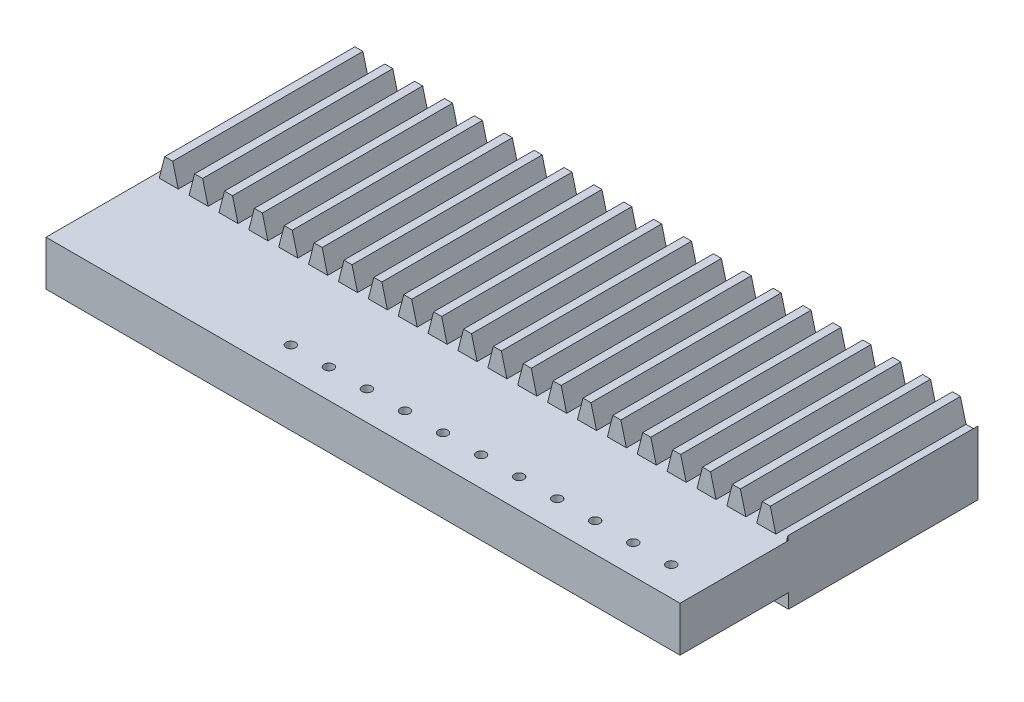
SolidWorks part; units mm, degrees
extrude "Blank" add sketch "BlankSke" against normal blind 20
sketch "BlankSke" plane through (0, 0, 0) normal (0, 0, 1) x (1, 0, 0)
  line L1 (0, 0) -> (100, 0)
  line L2 (0, 0) -> (0, 12.75)
  line L3 (0, 12.75) -> (100, 12.75)
  line L4 (100, 0) -> (100, 12.75)
  dimension "Length" = 100
ref_plane "Plane1" through (0, 0, 0) normal (0, 0, 1) x (1, 0, 0)
ref_plane "Plane2" through (0, 0, 0) normal (0, 1, 0) x (1, 0, 0)
ref_plane "Plane3" through (0, 0, 0) normal (1, 0, 0) x (0, 0, -1)
other "Configuration Table"
sketch "HoldingSke" plane through (0, 0, 0) normal (0, 1, 0) x (1, 0, 0)
  line L0 (0, 0) -> (0.0928, 0.6602)
  line L1 (-15, 0) -> (100, 0) construction
  line L2 (0, 0) -> (-2.1039, 2.3779)
  line L3 (0, 0) -> (-11.863, 4.5341)
  line L4 (0, 0) -> (7.9495, 3.3743)
  line L5 (0, 0) -> (-23.7986, -8.8762)
  line L6 (0, 0) -> (-10.5278, -7.1032)
  line L9 (-67.7845, 28.3722) -> (29.0302, 53.4102)
  line L10 (-76.2, 3.8779) -> (-64.95, 3.8779)
  line L11 (0, 0) -> (-20, 0)
  line L12 (-76.2, 101.6) -> (-76.147, 101.6)
  line L13 (24.9733, 27.94) -> (52.9518, 28.4284)
  line L14 (24.9733, 27.94) -> (24.9743, 27.94)
  line L15 (24.9733, 27.94) -> (100.4006, 29.5858)
  circle A0 centre (0, 0) radius 19.05
  circle A1 centre (0, 0) radius 5.625
  circle A2 centre (0, 0) radius 12.7
  dimension "Num_teeth" = 23
  dimension "Width" = 20
  dimension "Length" = 100
  dimension "Pitch_height" = 11.25
sketch "TooCutSkeIll" plane through (0, 0, 0) normal (0, 0, 1) x (1, 0, 0)
  line L0 (-1.7134, 12.705) -> (-0.9251, 9.6569)
  line L1 (-0.5611, 9.375) -> (0.5611, 9.375)
  line L2 (0.9251, 9.6569) -> (1.7134, 12.705)
  line L3 (100, 12.75) -> (0, 12.75) construction
  line L4 (0, 0) -> (0, 64.897) construction
  line L5 (-13.208, 11.25) -> (12.954, 11.25) construction
  line L6 (0, 0) -> (100, 0) construction
  line L7 (1.3371, 11.25) -> (1.3371, 48.7463) construction
  line L8 (-1.3371, 11.25) -> (-1.3371, 48.7463) construction
  line L9 (1.7715, 12.75) -> (1.7715, 12.7754)
  line L10 (-1.7715, 12.75) -> (-1.7715, 12.7754)
  line L11 (-1.7715, 12.7754) -> (1.7715, 12.7754)
  arc A0 (0.5611, 9.375) -> (0.9251, 9.6569) centre (0.5611, 9.751) ccw
  arc A1 (-0.9251, 9.6569) -> (-0.5611, 9.375) centre (-0.5611, 9.751) ccw
  arc A2 (1.7715, 12.75) -> (1.7134, 12.705) centre (1.7715, 12.69) ccw
  arc A3 (-1.7134, 12.705) -> (-1.7715, 12.75) centre (-1.7715, 12.69) ccw
  dimension "Addendum_plus" = 1.5254
  dimension "Pitch_height" = 11.25
  dimension "Pressure_angle" = 14.5
  dimension "Gap_width" = 2.6742
  dimension "Dedendum" = 1.875
extrude "ToothCutIll" [suppressed] cut sketch "TooCutSkeIll" against normal through all
sketch "TooCutSkeSim" plane through (0, 0, 0) normal (0, 0, 1) x (1, 0, 0)
  line L0 (0.8522, 9.375) -> (-0.8522, 9.375)
  line L1 (1.7316, 12.7754) -> (0.8522, 9.375)
  line L2 (0, 17.4625) -> (0, 53.467) construction
  line L3 (1.7316, 12.7754) -> (-1.7316, 12.7754)
  line L6 (-1.7316, 12.7754) -> (-0.8522, 9.375)
  line L9 (-1.3371, 11.25) -> (1.3371, 11.25) construction
  line L10 (0, 0) -> (100, 0) construction
  line L11 (1.3371, 11.25) -> (1.3371, 53.467) construction
  line L12 (-1.3371, 11.25) -> (-1.3371, 53.467) construction
  dimension "Addendum_plus" = 1.5254
  dimension "Pitch_height" = 11.25
  dimension "Pressure_angle" = 14.5
  dimension "Gap_width" = 2.6742
  dimension "Dedendum" = 1.875
extrude "ToothCutSim" cut sketch "TooCutSkeSim" against normal through all
pattern_linear "TeethCuts" count 23 spacing 4.7124 along (1, 0, 0) of "ToothCutIll", "ToothCutSim"
sketch "Croquis1" plane through (0, 0, 0) normal (0, 0, 1) x (1, 0, 0)
  line L89 (99.8124, 9.375) -> (98.108, 9.375)
  line L90 (98.108, 9.375) -> (97.2351, 12.75)
  line L91 (97.2351, 12.75) -> (95.9728, 12.75)
  line L92 (95.9728, 12.75) -> (95.1, 9.375)
  line L93 (95.1, 9.375) -> (93.3956, 9.375)
  line L94 (93.3956, 9.375) -> (92.5228, 12.75)
  line L95 (92.5228, 12.75) -> (91.2604, 12.75)
  line L96 (91.2604, 12.75) -> (90.3876, 9.375)
  line L97 (90.3876, 9.375) -> (88.6832, 9.375)
  line L98 (88.6832, 9.375) -> (87.8104, 12.75)
  line L99 (87.8104, 12.75) -> (86.548, 12.75)
  line L100 (86.548, 12.75) -> (85.6752, 9.375)
  line L101 (85.6752, 9.375) -> (83.9708, 9.375)
  line L102 (83.9708, 9.375) -> (83.098, 12.75)
  line L103 (83.098, 12.75) -> (81.8356, 12.75)
  line L104 (81.8356, 12.75) -> (80.9628, 9.375)
  line L105 (80.9628, 9.375) -> (79.2584, 9.375)
  line L106 (79.2584, 9.375) -> (78.3856, 12.75)
  line L107 (78.3856, 12.75) -> (77.1232, 12.75)
  line L108 (77.1232, 12.75) -> (76.2504, 9.375)
  line L109 (76.2504, 9.375) -> (74.546, 9.375)
  line L110 (74.546, 9.375) -> (73.6732, 12.75)
  line L111 (73.6732, 12.75) -> (72.4109, 12.75)
  line L112 (72.4109, 12.75) -> (71.538, 9.375)
  line L113 (71.538, 9.375) -> (69.8336, 9.375)
  line L114 (69.8336, 9.375) -> (68.9608, 12.75)
  line L115 (68.9608, 12.75) -> (67.6985, 12.75)
  line L116 (67.6985, 12.75) -> (66.8256, 9.375)
  line L117 (66.8256, 9.375) -> (65.1213, 9.375)
  line L118 (65.1213, 9.375) -> (64.2484, 12.75)
  line L119 (64.2484, 12.75) -> (62.9861, 12.75)
  line L120 (62.9861, 12.75) -> (62.1132, 9.375)
  line L121 (62.1132, 9.375) -> (60.4089, 9.375)
  line L122 (60.4089, 9.375) -> (59.536, 12.75)
  line L123 (59.536, 12.75) -> (58.2737, 12.75)
  line L124 (58.2737, 12.75) -> (57.4009, 9.375)
  line L125 (57.4009, 9.375) -> (55.6965, 9.375)
  line L126 (55.6965, 9.375) -> (54.8236, 12.75)
  line L127 (54.8236, 12.75) -> (53.5613, 12.75)
  line L128 (53.5613, 12.75) -> (52.6885, 9.375)
  line L129 (52.6885, 9.375) -> (50.9841, 9.375)
  line L130 (50.9841, 9.375) -> (50.1113, 12.75)
  line L131 (50.1113, 12.75) -> (48.8489, 12.75)
  line L132 (48.8489, 12.75) -> (47.9761, 9.375)
  line L133 (47.9761, 9.375) -> (46.2717, 9.375)
  line L134 (46.2717, 9.375) -> (45.3989, 12.75)
  line L135 (45.3989, 12.75) -> (44.1365, 12.75)
  line L136 (44.1365, 12.75) -> (43.2637, 9.375)
  line L137 (43.2637, 9.375) -> (41.5593, 9.375)
  line L138 (41.5593, 9.375) -> (40.6865, 12.75)
  line L139 (40.6865, 12.75) -> (39.4241, 12.75)
  line L140 (39.4241, 12.75) -> (38.5513, 9.375)
  line L141 (38.5513, 9.375) -> (36.8469, 9.375)
  line L142 (36.8469, 9.375) -> (35.9741, 12.75)
  line L143 (35.9741, 12.75) -> (34.7117, 12.75)
  line L144 (34.7117, 12.75) -> (33.8389, 9.375)
  line L145 (33.8389, 9.375) -> (32.1345, 9.375)
  line L146 (32.1345, 9.375) -> (31.2617, 12.75)
  line L147 (31.2617, 12.75) -> (29.9994, 12.75)
  line L148 (29.9994, 12.75) -> (29.1265, 9.375)
  line L149 (29.1265, 9.375) -> (27.4221, 9.375)
  line L150 (27.4221, 9.375) -> (26.5493, 12.75)
  line L151 (26.5493, 12.75) -> (25.287, 12.75)
  line L152 (25.287, 12.75) -> (24.4141, 9.375)
  line L153 (24.4141, 9.375) -> (22.7098, 9.375)
  line L154 (22.7098, 9.375) -> (21.8369, 12.75)
  line L155 (21.8369, 12.75) -> (20.5746, 12.75)
  line L156 (20.5746, 12.75) -> (19.7017, 9.375)
  line L157 (19.7017, 9.375) -> (17.9974, 9.375)
  line L158 (17.9974, 9.375) -> (17.1245, 12.75)
  line L159 (17.1245, 12.75) -> (15.8622, 12.75)
  line L160 (15.8622, 12.75) -> (14.9894, 9.375)
  line L161 (14.9894, 9.375) -> (13.285, 9.375)
  line L162 (13.285, 9.375) -> (12.4121, 12.75)
  line L163 (12.4121, 12.75) -> (11.1498, 12.75)
  line L164 (11.1498, 12.75) -> (10.277, 9.375)
  line L165 (10.277, 9.375) -> (8.5726, 9.375)
  line L166 (8.5726, 9.375) -> (7.6998, 12.75)
  line L167 (7.6998, 12.75) -> (6.4374, 12.75)
  line L168 (6.4374, 12.75) -> (5.5646, 9.375)
  line L169 (5.5646, 9.375) -> (3.8602, 9.375)
  line L170 (3.8602, 9.375) -> (2.9874, 12.75)
  line L171 (2.9874, 12.75) -> (1.725, 12.75)
  line L172 (1.725, 12.75) -> (0.8522, 9.375)
  line L173 (0.8522, 9.375) -> (0, 9.375)
  line L174 (0, 9.375) -> (0, 0)
  line L175 (0, 0) -> (100, 0)
  line L176 (100, 0) -> (100, 10.1006)
  line L177 (100, 10.1006) -> (99.8124, 9.375)
  line L178 (99.8124, 9.375) -> (98.108, 9.375)
  line L179 (98.108, 9.375) -> (97.2351, 12.75)
  line L180 (97.2351, 12.75) -> (95.9728, 12.75)
  line L181 (95.9728, 12.75) -> (95.1, 9.375)
  line L182 (95.1, 9.375) -> (93.3956, 9.375)
  line L183 (93.3956, 9.375) -> (92.5228, 12.75)
  line L184 (92.5228, 12.75) -> (91.2604, 12.75)
  line L185 (91.2604, 12.75) -> (90.3876, 9.375)
  line L186 (90.3876, 9.375) -> (88.6832, 9.375)
  line L187 (88.6832, 9.375) -> (87.8104, 12.75)
  line L188 (87.8104, 12.75) -> (86.548, 12.75)
  line L189 (86.548, 12.75) -> (85.6752, 9.375)
  line L190 (85.6752, 9.375) -> (83.9708, 9.375)
  line L191 (83.9708, 9.375) -> (83.098, 12.75)
  line L192 (83.098, 12.75) -> (81.8356, 12.75)
  line L193 (81.8356, 12.75) -> (80.9628, 9.375)
  line L194 (80.9628, 9.375) -> (79.2584, 9.375)
  line L195 (79.2584, 9.375) -> (78.3856, 12.75)
  line L196 (78.3856, 12.75) -> (77.1232, 12.75)
  line L197 (77.1232, 12.75) -> (76.2504, 9.375)
  line L198 (76.2504, 9.375) -> (74.546, 9.375)
  line L199 (74.546, 9.375) -> (73.6732, 12.75)
  line L200 (73.6732, 12.75) -> (72.4109, 12.75)
  line L201 (72.4109, 12.75) -> (71.538, 9.375)
  line L202 (71.538, 9.375) -> (69.8336, 9.375)
  line L203 (69.8336, 9.375) -> (68.9608, 12.75)
  line L204 (68.9608, 12.75) -> (67.6985, 12.75)
  line L205 (67.6985, 12.75) -> (66.8256, 9.375)
  line L206 (66.8256, 9.375) -> (65.1213, 9.375)
  line L207 (65.1213, 9.375) -> (64.2484, 12.75)
  line L208 (64.2484, 12.75) -> (62.9861, 12.75)
  line L209 (62.9861, 12.75) -> (62.1132, 9.375)
  line L210 (62.1132, 9.375) -> (60.4089, 9.375)
  line L211 (60.4089, 9.375) -> (59.536, 12.75)
  line L212 (59.536, 12.75) -> (58.2737, 12.75)
  line L213 (58.2737, 12.75) -> (57.4009, 9.375)
  line L214 (57.4009, 9.375) -> (55.6965, 9.375)
  line L215 (55.6965, 9.375) -> (54.8236, 12.75)
  line L216 (54.8236, 12.75) -> (53.5613, 12.75)
  line L217 (53.5613, 12.75) -> (52.6885, 9.375)
  line L218 (52.6885, 9.375) -> (50.9841, 9.375)
  line L219 (50.9841, 9.375) -> (50.1113, 12.75)
  line L220 (50.1113, 12.75) -> (48.8489, 12.75)
  line L221 (48.8489, 12.75) -> (47.9761, 9.375)
  line L222 (47.9761, 9.375) -> (46.2717, 9.375)
  line L223 (46.2717, 9.375) -> (45.3989, 12.75)
  line L224 (45.3989, 12.75) -> (44.1365, 12.75)
  line L225 (44.1365, 12.75) -> (43.2637, 9.375)
  line L226 (43.2637, 9.375) -> (41.5593, 9.375)
  line L227 (41.5593, 9.375) -> (40.6865, 12.75)
  line L228 (40.6865, 12.75) -> (39.4241, 12.75)
  line L229 (39.4241, 12.75) -> (38.5513, 9.375)
  line L230 (38.5513, 9.375) -> (36.8469, 9.375)
  line L231 (36.8469, 9.375) -> (35.9741, 12.75)
  line L232 (35.9741, 12.75) -> (34.7117, 12.75)
  line L233 (34.7117, 12.75) -> (33.8389, 9.375)
  line L234 (33.8389, 9.375) -> (32.1345, 9.375)
  line L235 (32.1345, 9.375) -> (31.2617, 12.75)
  line L236 (31.2617, 12.75) -> (29.9994, 12.75)
  line L237 (29.9994, 12.75) -> (29.1265, 9.375)
  line L238 (29.1265, 9.375) -> (27.4221, 9.375)
  line L239 (27.4221, 9.375) -> (26.5493, 12.75)
  line L240 (26.5493, 12.75) -> (25.287, 12.75)
  line L241 (25.287, 12.75) -> (24.4141, 9.375)
  line L242 (24.4141, 9.375) -> (22.7098, 9.375)
  line L243 (22.7098, 9.375) -> (21.8369, 12.75)
  line L244 (21.8369, 12.75) -> (20.5746, 12.75)
  line L245 (20.5746, 12.75) -> (19.7017, 9.375)
  line L246 (19.7017, 9.375) -> (17.9974, 9.375)
  line L247 (17.9974, 9.375) -> (17.1245, 12.75)
  line L248 (17.1245, 12.75) -> (15.8622, 12.75)
  line L249 (15.8622, 12.75) -> (14.9894, 9.375)
  line L250 (14.9894, 9.375) -> (13.285, 9.375)
  line L251 (13.285, 9.375) -> (12.4121, 12.75)
  line L252 (12.4121, 12.75) -> (11.1498, 12.75)
  line L253 (11.1498, 12.75) -> (10.277, 9.375)
  line L254 (10.277, 9.375) -> (8.5726, 9.375)
  line L255 (8.5726, 9.375) -> (7.6998, 12.75)
  line L256 (7.6998, 12.75) -> (6.4374, 12.75)
  line L257 (6.4374, 12.75) -> (5.5646, 9.375)
  line L258 (5.5646, 9.375) -> (3.8602, 9.375)
  line L259 (3.8602, 9.375) -> (2.9874, 12.75)
  line L260 (2.9874, 12.75) -> (1.725, 12.75)
  line L261 (1.725, 12.75) -> (0.8522, 9.375)
  line L262 (0.8522, 9.375) -> (0, 9.375)
  line L263 (0, 9.375) -> (0, 0)
  line L264 (0, 0) -> (100, 0)
  line L265 (100, 0) -> (100, 10.1006)
  line L266 (100, 10.1006) -> (99.8124, 9.375)
  dimension "D1" = 0
extrude "Saliente-Extruir1" add sketch "Croquis1" along normal blind 10
sketch "Croquis2" plane through (0, 0, -20) normal (0, 0, -1) x (-1, 0, 0)
  line L1 (-100, 0) -> (0, 0)
  line L2 (-100, 0) -> (-100, 9.375)
  line L3 (-100, 9.375) -> (0, 9.375)
  line L4 (0, 0) -> (0, 9.375)
sketch "Croquis3" plane through (0, 0, 10) normal (0, 0, 1) x (1, 0, 0)
  line L1 (100, 0) -> (0, 0)
  line L2 (100, 0) -> (100, 9.375)
  line L3 (100, 9.375) -> (0, 9.375)
  line L4 (0, 0) -> (0, 9.375)
extrude "Saliente-Extruir3" add sketch "Croquis3" along normal blind 17
sketch "Croquis4" plane through (100, 0, 0) normal (1, 0, 0) x (0, 0, -1)
  line L1 (-27, 0) -> (-9.8954, 0)
  line L2 (-27, 0) -> (-27, 2.275)
  line L3 (-27, 2.275) -> (-9.8954, 2.275)
  line L4 (-9.8954, 0) -> (-9.8954, 2.275)
  dimension "D1" = 2.275
extrude "Cortar-Extruir1" cut sketch "Croquis4" against normal through all
sketch "Croquis5" plane through (0, 9.375, 0) normal (0, 1, 0) x (1, 0, 0)
  line L3 (99.9869, -23.9108) -> (29.9869, -23.9108)
  line L4 (99.9869, -20.9108) -> (29.9869, -20.9108)
  line L5 (29.9869, -20.9108) -> (29.9869, -23.9108)
sketch "Croquis8" plane through (0, 9.375, 0) normal (0, 1, 0) x (1, 0, 0)
  circle A11 centre (64.03, -22.4108) radius 0.75
  circle A12 centre (70.03, -22.4108) radius 0.75
  circle A13 centre (76.03, -22.4108) radius 0.75
  circle A14 centre (82.03, -22.4108) radius 0.75
  circle A15 centre (88.03, -22.4108) radius 0.75
  circle A16 centre (94.03, -22.4108) radius 0.75
  circle A17 centre (58.03, -22.4108) radius 0.75
  circle A18 centre (52.03, -22.4108) radius 0.75
  circle A19 centre (46.03, -22.4108) radius 0.75
  circle A20 centre (40.03, -22.4108) radius 0.75
  circle A21 centre (34.03, -22.4108) radius 0.75
extrude "Cortar-Extruir3" cut sketch "Croquis8" against normal blind 6
equation "' \"Module@HoldingSke\" = 6.35"
equation "' \"Num_teeth@HoldingSke\" = 12"
equation "' \"Ap@HoldingSke\" =  20"
equation "' \"Ap@HoldingSke\" = 20"
equation "' \"Width@HoldingSke\" = 0.25 * 25.4"
equation "' \"Show_teeth@HoldingSke\" = 500"
equation "' \"Backlash@HoldingSke\" = 0.009 * 25.4"
equation "' \"Addendum_fac@HoldingSke\" = 1.0"
equation "' \"Dedendum_fac@HoldingSke\" = 1.25"
equation "' \"Dedendum_add@HoldingSke\" = 0.00005 * 25.4"
equation "' \"Clearance_fac@HoldingSke\" = 0.25"
equation "' \"Pitch_height@HoldingSke\" = 1 * 25.4"
equation "' \"Length@HoldingSke\" = 4.71 * 25.4"
equation "\"Pitch@HoldingSke\" = 1 / \"Module@HoldingSke\""
equation "\"MPH@HoldingSke\" = \"Dedendum_fac@HoldingSke\" / \"Pitch@HoldingSke\" + 2 * \"Dedendum_add@HoldingSke\" + 0.002 * 25.4"
equation "\"MPH@HoldingSke\" = ((sgn( \"MPH@HoldingSke\" - \"Pitch_height@HoldingSke\")+1)*( \"MPH@HoldingSke\" - \"Pitch_height@HoldingSke\"))/2 + \"Pitch_height@HoldingSke\""
equation "\"Blank_height@BlankSke\" = \"Pitch_height@HoldingSke\" + \"Addendum_fac@HoldingSke\"  / \"Pitch@HoldingSke\" "
equation "\"Length@BlankSke\" =  \"Length@HoldingSke\""
equation "\"Face_width@Blank\" = \"Width@HoldingSke\""
equation "\"Pressure_angle@TooCutSkeIll\" = \"Ap@HoldingSke\""
equation "\"Addendum_plus@TooCutSkeIll\" =  \"Addendum_fac@HoldingSke\"  / \"Pitch@HoldingSke\" + 0.001 *25.4"
equation "\"Dedendum@TooCutSkeIll\" = \"Dedendum_fac@HoldingSke\"  / \"Pitch@HoldingSke\""
equation "\"Pitch_height@TooCutSkeIll\" =  \"MPH@HoldingSke\""
equation "\"Gap_width@TooCutSkeIll\" = 3.14159265 / 2 / \"Pitch@HoldingSke\" + 6 * \"Backlash@HoldingSke\""
equation "\"Pressure_angle@TooCutSkeSim\" = \"Ap@HoldingSke\""
equation "\"Addendum_plus@TooCutSkeSim\" =  \"Addendum_fac@HoldingSke\"  / \"Pitch@HoldingSke\" + 0.001 * 25.4"
equation "\"Dedendum@TooCutSkeSim\" = \"Dedendum_fac@HoldingSke\"  / \"Pitch@HoldingSke\""
equation "\"Pitch_height@TooCutSkeSim\" =  \"MPH@HoldingSke\""
equation "\"Gap_width@TooCutSkeSim\" = 3.14159265 / 2 / \"Pitch@HoldingSke\" + 6 * \"Backlash@HoldingSke\""
equation "\"Root_fillet@TooCutSkeIll\" = \"Clearance_fac@HoldingSke\" / \"Pitch@HoldingSke\" + \"Dedendum_add@HoldingSke\""
equation "\"Break_rad@TooCutSkeIll\" = 0.02 / \"Pitch@HoldingSke\" * 2"
equation "\"Linear_pitch@TeethCuts\" = 3.14159265 / \"Pitch@HoldingSke\""
equation "\"Num_teeth@HoldingSke\" = int( ( \"Length@HoldingSke\" + 0 ) / (3.14159265 / \"Pitch@HoldingSke\")) + 0.9999  + 1"
equation " \"Num_teeth@TeethCuts\" = int( \"Show_teeth@HoldingSke\" ) + 1"
equation " \"Num_teeth@TeethCuts\" = ((sgn( \"Num_teeth@TeethCuts\" - \"Num_teeth@HoldingSke\" )-1)*( \"Num_teeth@TeethCuts\" - \"Num_teeth@HoldingSke\" ))/-2+ \"Num_teeth@HoldingSke\""
equation " \"Num_teeth@TeethCuts\" = ((sgn( \"Num_teeth@TeethCuts\" - 2.0)+1)*( \"Num_teeth@TeethCuts\" - 2.0))/2 +2.0"
